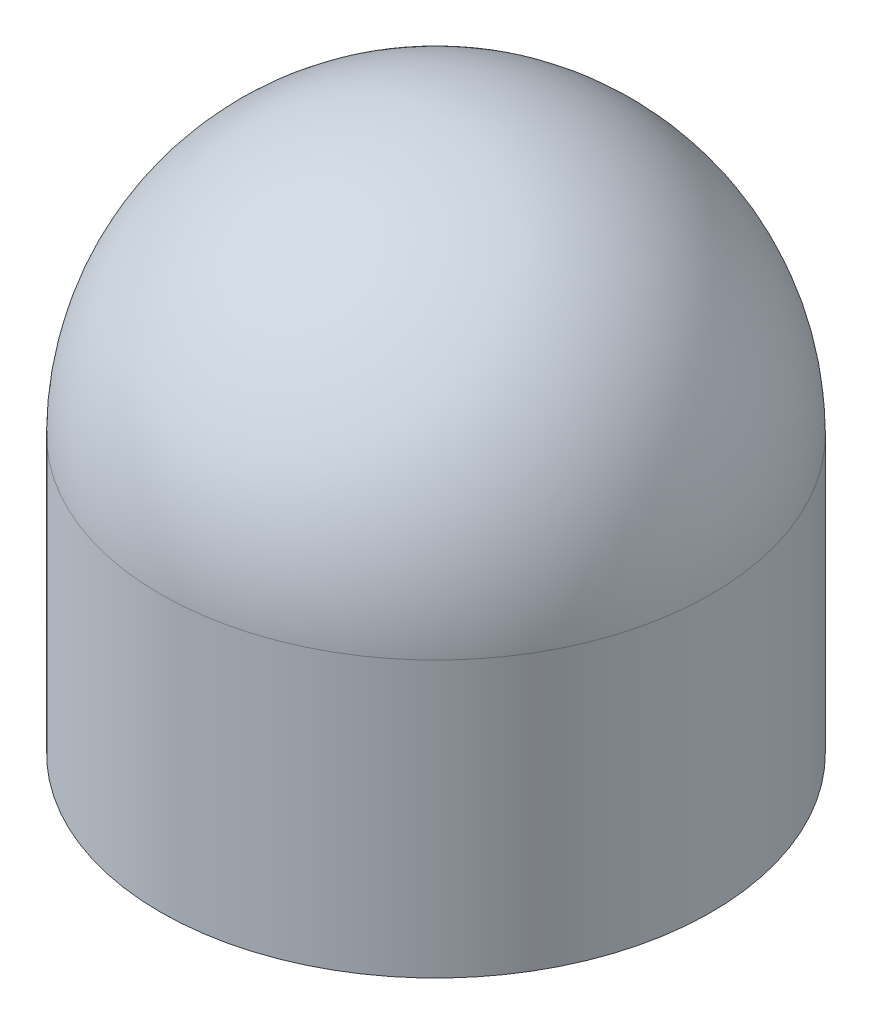
SolidWorks part; units mm, degrees
ref_plane "前视基准面" through (0, 0, 0) normal (0, 0, 1) x (1, 0, 0)
ref_plane "上视基准面" through (0, 0, 0) normal (0, 1, 0) x (1, 0, 0)
ref_plane "右视基准面" through (0, 0, 0) normal (1, 0, 0) x (0, 0, -1)
sketch "草图1" plane through (0, 0, 0) normal (0, 1, 0) x (1, 0, 0)
  circle A0 centre (0, 0) radius 0.125
  dimension "D1" = 0.25
extrude "凸台-拉伸1" add sketch "草图1" along normal blind 0.125
dome "圆顶1" faces to dome 1 distance 0.125 reverse direction no elliptical dome no face at (0, 0.125, 0.125) parameters "D1"=0.125
